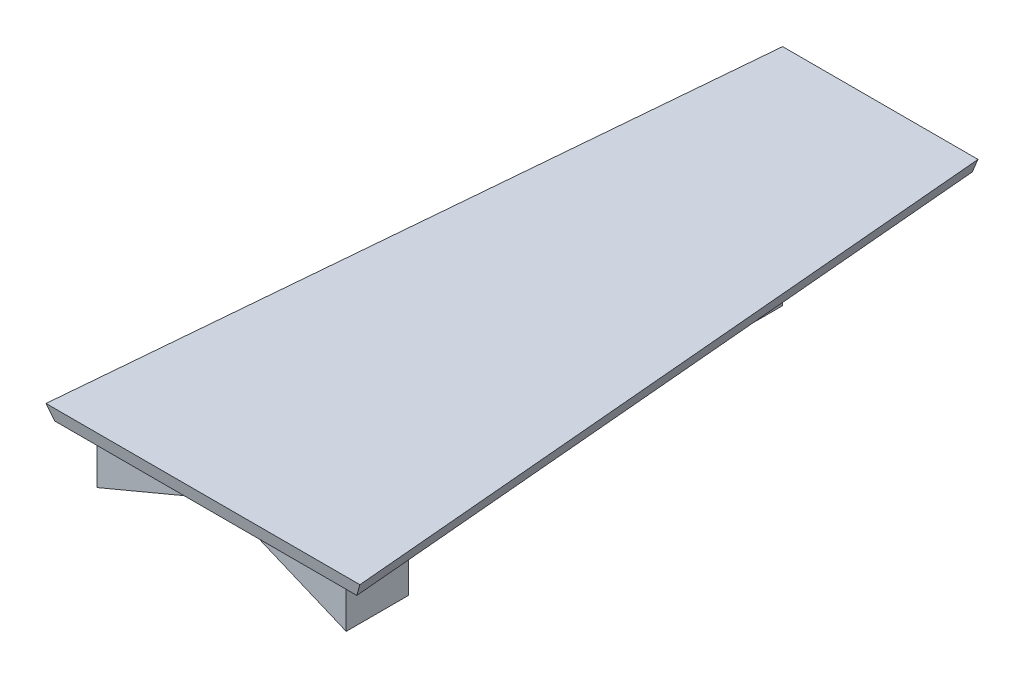
SolidWorks part; units mm, degrees
ref_plane "Ebene vorne" through (0, 0, 0) normal (0, 0, 1) x (1, 0, 0)
ref_plane "Ebene oben" through (0, 0, 0) normal (0, 1, 0) x (1, 0, 0)
ref_plane "Ebene rechts" through (0, 0, 0) normal (1, 0, 0) x (0, 0, -1)
sketch "Skizze1" plane through (0, 0, 0) normal (0, 1, 0) x (1, 0, 0)
  line L1 (-28.5, -61.5) -> (28.5, -61.5)
  line L2 (-28.5, -61.5) -> (-28.5, 61.5)
  line L3 (-28.5, 61.5) -> (28.5, 61.5)
  line L4 (28.5, -61.5) -> (28.5, 61.5)
  line L5 (-28.5, -61.5) -> (28.5, 61.5) construction
  line L6 (-28.5, 61.5) -> (28.5, -61.5) construction
  point P0 (0, 0)
  dimension "D1" = 57
  dimension "D2" = 123
extrude "Aufsatz-Linear austragen1" add sketch "Skizze1" along normal blind 2.5
sketch "Skizze2" plane through (28.5, 0, 0) normal (1, 0, 0) x (0, 0, -1)
  line L0 (-61.5, 2.5) -> (-61.5, 0)
  line L1 (55, 0) -> (-55, 0) construction
  line L2 (-61.5, 2.5) -> (-61.5, 0) construction
  line L3 (-61.5, 0) -> (-60.9686, 0)
  line L4 (-60.9686, 0) -> (-61.5, 2.5)
  dimension "D1" = 102
extrude "Schnitt-Linear austragen1" cut sketch "Skizze2" against normal through all
sketch "Skizze3" plane through (0, 2.5, 0) normal (0, 1, 0) x (1, 0, 0)
  line L0 (-28.5, -61.5) -> (-17.7389, 61.5)
  line L1 (28.5, 61.5) -> (-28.5, 61.5) construction
  line L2 (-17.7389, 61.5) -> (-28.5, 61.5)
  line L3 (-28.5, 61.5) -> (-28.5, -61.5)
  line L4 (28.5, -61.5) -> (17.7389, 61.5)
  line L5 (17.7389, 61.5) -> (28.5, 61.5)
  line L6 (28.5, 61.5) -> (28.5, -61.5)
  dimension "D1" = 95
  dimension "D2" = 95
extrude "Schnitt-Linear austragen2" cut sketch "Skizze3" against normal through all
ref_axis "Achse1" through (23.1194, 2.5, 0) along (0, -1, 0)
ref_plane "Ebene1" through (0.1756, 0, 2.0073) normal (0.0872, 0, 0.9962) x (0, -1, 0)
sketch "Skizze5" plane through (0.1756, 0, 2.0073) normal (0.0872, 0, 0.9962) x (0, -1, 0)
  line L0 (0.0086, 23.0315) -> (-2.5, 23.0315)
  line L1 (-2.5, 23.0315) -> (0, 23.0315) construction
  line L5 (0.0086, 23.0315) -> (0, 21.9959)
  line L6 (0, -33.659) -> (0, 23.0315) construction
  line L7 (0, 21.9959) -> (-2.5, 23.0315)
  line L8 (-2.5, -33.7516) -> (-2.5, 23.0315) construction
  dimension "D1" = 67.5
extrude "Schnitt-Linear austragen3" cut sketch "Skizze5" against normal through all and the other way through all
ref_axis "Achse2" through (-23.0962, -8.4274, -0.2657) along (0, 1, 0)
ref_plane "Ebene2" through (-0.1524, 0, 1.7416) normal (-0.0872, 0, 0.9962) x (0, 1, 0)
sketch "Skizze6" plane through (-0.1524, 0, 1.7416) normal (-0.0872, 0, 0.9962) x (0, 1, 0)
  line L1 (2.5, 23.0315) -> (0, 21.9959)
  line L2 (0, -55) -> (0, 55) construction
  line L3 (0, 21.9959) -> (0, 23.0315)
  line L4 (0, 23.0315) -> (2.5, 23.0315)
  line L5 (2.5, 23.0315) -> (2.5, -33.7516) construction
  dimension "D1" = 67.5
extrude "Schnitt-Linear austragen4" cut sketch "Skizze6" against normal through all and the other way through all
sketch "Skizze9" plane through (0, 0, 0) normal (0, -1, 0) x (1, 0, 0)
  line L6 (0, -61.5) -> (0, 60.9686) construction
  line L11 (16.6994, -61.5) -> (-16.6994, -61.5) construction
  line L12 (-27.414, 60.9686) -> (27.414, 60.9686) construction
  line L13 (0, 52.4686) -> (-26.6704, 52.4686) construction
  line L14 (-16.6994, -61.5) -> (-27.414, 60.9686) construction
  line L15 (-26.6704, 52.4686) -> (26.6704, 52.4686) construction
  line L16 (16.6994, -61.5) -> (27.414, 60.9686) construction
  line L17 (0, -19.5) -> (-20.3739, -19.5) construction
  line L18 (-20.3739, -19.5) -> (20.3739, -19.5) construction
  line L20 (22.6207, 58.1089) -> (-22.6207, 58.1089)
  line L21 (22.6207, 58.1089) -> (22.6207, 46.8283)
  line L22 (22.6207, 46.8283) -> (-22.6207, 46.8283)
  line L23 (-22.6207, 58.1089) -> (-22.6207, 46.8283)
  line L24 (22.6207, 58.1089) -> (-22.6207, 46.8283) construction
  line L25 (22.6207, 46.8283) -> (-22.6207, 58.1089) construction
  dimension "D1" = 42
  dimension "D2" = 8.5
extrude "Aufsatz-Linear austragen2" add sketch "Skizze9" along normal blind 13 contours L21 L20 L23 L22
sketch "Skizze11" plane through (0, 0, 46.8283) normal (0, 0, -1) x (-1, 0, 0)
  line L0 (-22.6207, -9.484) -> (0, 0)
  line L1 (-22.6207, -13) -> (-22.6207, 0) construction
  line L2 (-22.6207, 0) -> (22.6207, 0) construction
  line L3 (0, 0) -> (22.6207, -9.484)
  line L4 (22.6207, -13) -> (22.6207, 0) construction
  line L5 (22.6207, -9.484) -> (22.6207, -13)
  line L6 (22.6207, -13) -> (-22.6207, -13)
  line L7 (-22.6207, -13) -> (-22.6207, -9.484)
extrude "Schnitt-Linear austragen5" cut sketch "Skizze11" against normal blind 20
sketch "Skizze12" plane through (0, 0, 0) normal (0, -1, 0) x (1, 0, 0)
  line L0 (0, -61.5) -> (0, -2.1503) construction
  line L5 (16.6994, -61.5) -> (-16.6994, -61.5) construction
  line L6 (-20.3739, -19.5) -> (20.3739, -19.5) construction
  line L12 (-16.6994, -61.5) -> (-27.414, 60.9686) construction
  line L13 (16.6994, -61.5) -> (27.414, 60.9686) construction
  line L15 (18.0118, -15.2638) -> (-18.0118, -15.2638)
  line L16 (18.0118, -15.2638) -> (18.0118, -25.7362)
  line L17 (18.0118, -25.7362) -> (-18.0118, -25.7362)
  line L18 (-18.0118, -15.2638) -> (-18.0118, -25.7362)
  line L19 (18.0118, -15.2638) -> (-18.0118, -25.7362) construction
  line L24 (18.0118, -25.7362) -> (-18.0118, -15.2638) construction
  point P10 (0, -20.5)
  dimension "D2" = 41
extrude "Aufsatz-Linear austragen3" add sketch "Skizze12" along normal blind 5
sketch "Skizze13" plane through (0, 0, -25.7362) normal (0, 0, -1) x (-1, 0, 0)
  line L0 (-18.0118, -2.5) -> (-7.1831, 0)
  line L3 (-18.0118, -5) -> (-18.0118, 0) construction
  line L4 (18.0118, 0) -> (-18.0118, 0) construction
  line L5 (-7.1831, 0) -> (7.1831, 0)
  line L6 (7.1831, 0) -> (18.0118, -2.5)
  line L7 (18.0118, -5) -> (18.0118, 0) construction
  line L8 (18.0118, -2.5) -> (18.0118, -5)
  line L9 (18.0118, -5) -> (-18.0118, -5)
  line L10 (-18.0118, -5) -> (-18.0118, -2.5)
  dimension "D1" = 103
  dimension "D2" = 103
extrude "Schnitt-Linear austragen6" cut sketch "Skizze13" against normal blind 12
sketch "Skizze16" plane through (0, 0, 0) normal (0, -1, 0) x (1, 0, 0)
  line L0 (7.1831, -25.7362) -> (18.0118, -15.2638) construction
  line L1 (18.0118, -15.2638) -> (-18.0118, -15.2638) construction
  line L2 (-18.0118, -15.2638) -> (-7.1831, -25.7362) construction
  circle A0 centre (12.5975, -20.5) radius 3.1
  circle A1 centre (-12.5975, -20.5) radius 3.1
  dimension "D1" = 6.2
  dimension "D2" = 6.2
extrude "Schnitt-Linear austragen8" cut sketch "Skizze16" against normal blind 1.65 and the other way blind 0.5
ref_plane "Ebene7" through (0, -4.742, 0) normal (0, 1, 0) x (1, 0, 0)
sketch "Skizze17" plane through (0, -4.742, 0) normal (0, 1, 0) x (1, 0, 0)
  line L0 (22.6207, -58.1089) -> (11.3104, -46.8283) construction
  line L1 (0, -46.8283) -> (22.6207, -46.8283) construction
  line L2 (11.3104, -46.8283) -> (-11.3104, -58.1089) construction
  line L3 (-22.6207, -58.1089) -> (0, -58.1089) construction
  line L4 (-11.3104, -58.1089) -> (-22.6207, -46.8283) construction
  circle A0 centre (-16.9656, -52.4686) radius 3.1
  circle A1 centre (16.9656, -52.4686) radius 3.1
  dimension "D1" = 6.2
  dimension "D2" = 6.2
extrude "Schnitt-Linear austragen9" cut sketch "Skizze17" against normal blind 1 and the other way blind 1.15
